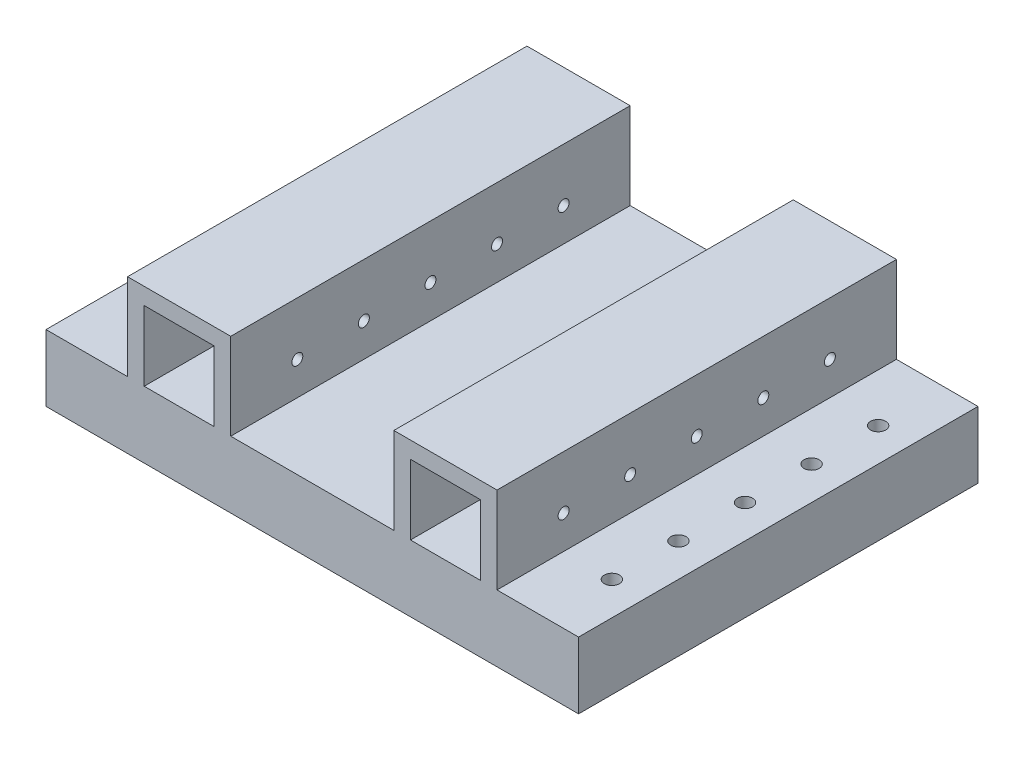
SolidWorks part; units mm, degrees
ref_plane "前视基准面" through (0, 0, 0) normal (0, 0, 1) x (1, 0, 0)
ref_plane "上视基准面" through (0, 0, 0) normal (0, 1, 0) x (1, 0, 0)
ref_plane "右视基准面" through (0, 0, 0) normal (1, 0, 0) x (0, 0, -1)
other "Configuration Table"
sketch "草图1" plane through (0, 0, 0) normal (0, 0, 1) x (1, 0, 0)
  line L0 (-80, 0) -> (80, 0)
  line L1 (80, 0) -> (80, 20)
  line L2 (80, 20) -> (55.5, 20)
  line L3 (55.5, 20) -> (55.5, 46)
  line L4 (55.5, 46) -> (24.5, 46)
  line L5 (24.5, 46) -> (24.5, 20)
  line L6 (24.5, 20) -> (-24.5, 20)
  line L7 (0, -55) -> (0, 55) construction
  line L8 (29.5, 41) -> (50.5, 41)
  line L9 (29.5, 41) -> (29.5, 20)
  line L10 (29.5, 20) -> (50.5, 20)
  line L11 (50.5, 41) -> (50.5, 20)
  line L12 (29.5, 41) -> (50.5, 20) construction
  line L13 (29.5, 20) -> (50.5, 41) construction
  line L14 (-29.5, 20) -> (-50.5, 41) construction
  line L15 (-29.5, 41) -> (-50.5, 20) construction
  line L16 (-50.5, 41) -> (-50.5, 20)
  line L17 (-29.5, 20) -> (-50.5, 20)
  line L18 (-29.5, 41) -> (-29.5, 20)
  line L19 (-29.5, 41) -> (-50.5, 41)
  line L20 (-24.5, 46) -> (-24.5, 20)
  line L21 (-55.5, 46) -> (-24.5, 46)
  line L22 (-55.5, 20) -> (-55.5, 46)
  line L23 (-80, 20) -> (-55.5, 20)
  line L24 (-80, 0) -> (-80, 20)
  point P0 (-40, 30.5)
  point P3 (40, 30.5)
  point P29 (0, 20)
  point P34 (0, 0)
  dimension "D1" = 80
  dimension "D2" = 20
  dimension "D3" = 20
  dimension "D4" = 31
  dimension "D5" = 5
  dimension "D6" = 21
  dimension "D7" = 21
  dimension "D9" = 5
  dimension "D10" = 29.5
extrude "凸台-拉伸1" add sketch "草图1" along normal blind 120
sketch "草图2" plane through (0, 0, 0) normal (0, -1, 0) x (1, 0, 0)
  line L0 (-80, 60) -> (80, 60) construction
  line L1 (-80, 120) -> (-80, 0) construction
  line L2 (80, 120) -> (80, 0) construction
  line L3 (0, 120) -> (0, 0) construction
  line L4 (-80, 120) -> (80, 120) construction
  line L5 (-80, 0) -> (80, 0) construction
  line L7 (-43, 97.5) -> (43, 97.5)
  line L8 (-43, 97.5) -> (-43, 22.5)
  line L9 (-43, 22.5) -> (43, 22.5)
  line L10 (43, 97.5) -> (43, 22.5)
  line L11 (-43, 97.5) -> (43, 22.5) construction
  line L12 (-43, 22.5) -> (43, 97.5) construction
  point P12 (0, 60)
  dimension "D1" = 75
  dimension "D2" = 86
extrude "切除-拉伸1" cut sketch "草图2" against normal blind 16
sketch "草图3" plane through (-55.5, 0, 0) normal (-1, 0, 0) x (0, 0, 1)
  line L0 (120, 20) -> (0, 20) construction
  line L1 (0, 46) -> (0, 20) construction
  circle A0 centre (20, 30) radius 1.65
  circle A1 centre (40, 30) radius 1.65
  circle A2 centre (60, 30) radius 1.65
  circle A3 centre (80, 30) radius 1.65
  circle A4 centre (100, 30) radius 1.65
  dimension "D1" = 3.3
  dimension "D2" = 20
  dimension "D4" = 10
  dimension "D3" = 5
extrude "切除-拉伸2" cut sketch "草图3" against normal through all
sketch "草图5" plane through (0, 0, 0) normal (0, -1, 0) x (1, 0, 0)
  line L0 (0, 0) -> (0, 25.3851) construction
  line L1 (-80, 0) -> (80, 0) construction
  line L2 (-80, 120) -> (-80, 0) construction
  line L3 (-80, 120) -> (80, 120) construction
  circle A0 centre (-70, 100) radius 2.2755
  circle A1 centre (-70, 80) radius 2.2755
  circle A2 centre (-70, 60) radius 2.2755
  circle A3 centre (-70, 40) radius 2.2755
  circle A4 centre (-70, 20) radius 2.2755
  dimension "D1" = 10
  dimension "D2" = 20
  dimension "D3" = 5
extrude "切除-拉伸3" cut sketch "草图5" against normal through all
mirror "镜向1" about plane through (0, 0, 0) normal (1, 0, 0) of "切除-拉伸3"
